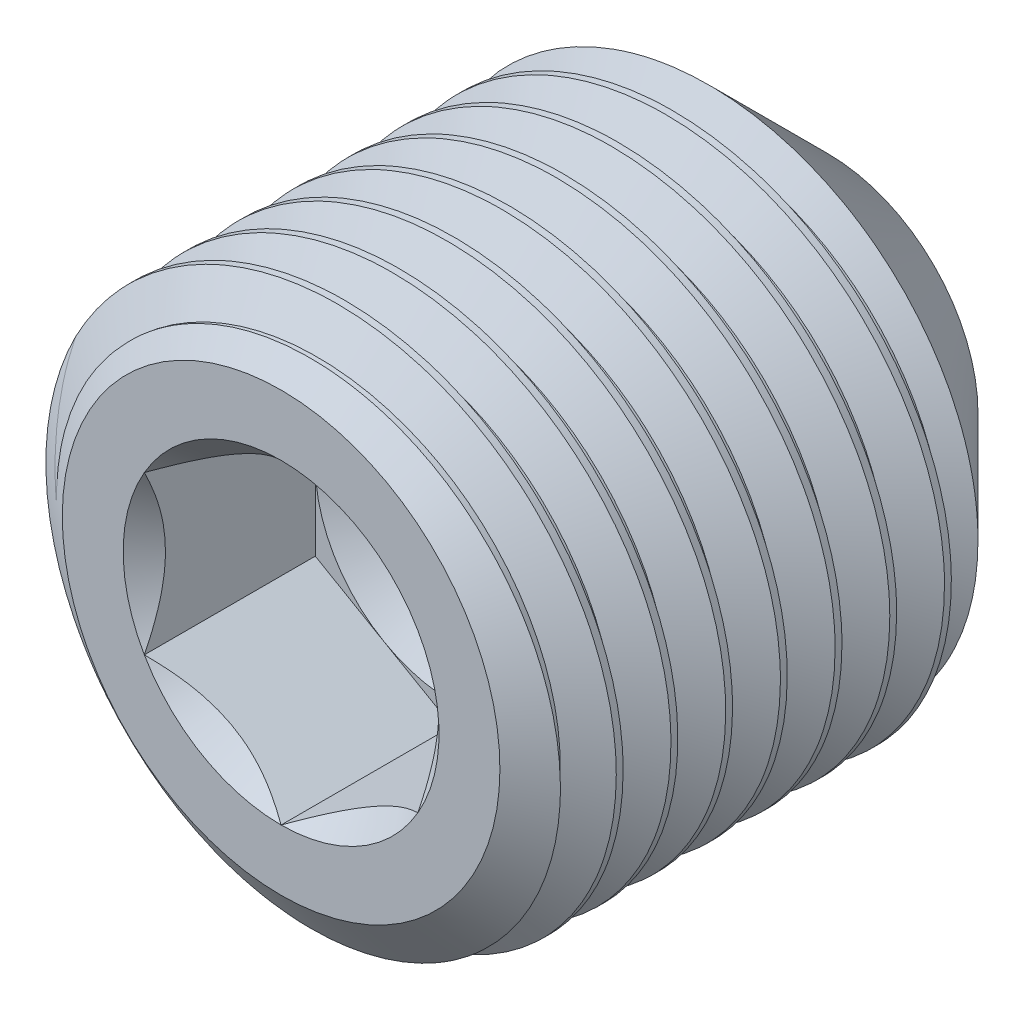
SolidWorks part; units mm, degrees
ref_plane "Front" through (0, 0, 0) normal (0, 0, 1) x (1, 0, 0)
ref_plane "Top" through (0, 0, 0) normal (0, 1, 0) x (1, 0, 0)
ref_plane "Right" through (0, 0, 0) normal (1, 0, 0) x (0, 0, -1)
sketch "Sketch22" plane through (0, 0, 0) normal (1, 0, 0) x (0, 0, -1)
  line L0 (-5.3046, 0) -> (-5.3046, 5.08)
  line L1 (-5.3046, 5.08) -> (-4.4154, 6.35)
  line L2 (-4.4154, 6.35) -> (4.5249, 6.35)
  line L3 (4.5249, 6.35) -> (7.3954, 3.4796)
  line L4 (7.3954, 3.4796) -> (5.3046, 0)
  line L5 (5.3046, 0) -> (-5.3046, 0)
  line L6 (5.3046, 0) -> (7.3954, 0) construction
  line L7 (7.3954, 0) -> (7.3954, 3.4796) construction
  line L8 (7.3954, -3.4796) -> (5.3046, 0) construction
  line L9 (-4.4154, -6.35) -> (4.5249, -6.35) construction
  dimension "Dia" = 12.7
  dimension "Length" = 12.7
  dimension "D3" = 35
  dimension "D5" = 118
  dimension "D6" = 45
  dimension "D7" = 10.16
revolve "Revolve1" add sketch "Sketch22" angle 360 about L6
ref_plane "Plane1" through (0, 0, -7.3954) normal (0, 0, 1) x (1, 0, 0)
sketch "Sketch27" plane through (0, 0, -7.3954) normal (0, 0, 1) x (1, 0, 0)
  circle A0 centre (0, 0) radius 6.35 construction
  circle A1 centre (0, 0) radius 6.35
curve "Helix/Spiral1" pitch 1.27 height 13.97 radius 6.35 centre (0, 0, -7.3954) axis (0, 0, 1) start towards (0, 1, 0)
sketch "Sketch28" plane through (0, 0, 0) normal (1, 0, 0) x (0, 0, -1)
  line L0 (7.3954, 6.35) -> (8.5066, 6.35)
  line L1 (8.5066, 6.35) -> (8.0304, 5.5251)
  line L2 (8.0304, 5.5251) -> (7.8716, 5.5251)
  line L3 (7.8716, 5.5251) -> (7.3954, 6.35)
  line L4 (7.6335, 5.9376) -> (8.2685, 5.9376) construction
  line L6 (-4.4154, 6.35) -> (4.5249, 6.35) construction
  line L7 (7.3954, 6.985) -> (7.3954, -6.985) construction
  dimension "D1" = 0.1588
  dimension "D2" = 0.635
  dimension "D3" = 60
sweep "Cut-Sweep2" cut profiles "Sketch28" path "Helix/Spiral1"
sketch "Sketch23" plane through (0, 0, 5.3046) normal (0, 0, 1) x (1, 0, 0)
  line L1 (0, 3.6662) -> (-3.175, 1.8331)
  line L2 (-3.175, 1.8331) -> (-3.175, -1.8331)
  line L3 (-3.175, -1.8331) -> (0, -3.6662)
  line L4 (0, -3.6662) -> (3.175, -1.8331)
  line L5 (3.175, -1.8331) -> (3.175, 1.8331)
  line L6 (3.175, 1.8331) -> (0, 3.6662)
  circle A0 centre (0, 0) radius 3.175 construction
  dimension "Hex" = 6.35
extrude "Cut-Extrude10" cut sketch "Sketch23" against normal blind 3.9688
sketch "Sketch24" plane through (0, 0, 5.3046) normal (0, 0, 1) x (1, 0, 0)
  circle A0 centre (0, 0) radius 3.6662
extrude "Cut-Extrude11" cut sketch "Sketch24" against normal through all draft 45
sketch "Sketch26" plane through (0, 0, 1.3359) normal (0, 0, 1) x (1, 0, 0)
  circle A0 centre (0, 0) radius 3.175 construction
  circle A1 centre (0, 0) radius 3.175
extrude "Cut-Extrude12" cut sketch "Sketch26" against normal through all draft 60
sketch "Sketch30" plane through (0, 0, 0) normal (1, 0, 0) x (0, 0, -1)
  line L0 (-4.4154, 6.35) -> (4.5249, 6.35) construction
  line L1 (-5.3046, 0) -> (-5.3046, 5.08) construction
  line L2 (7.3954, 0) -> (7.3954, 3.4796) construction
  line L3 (-4.4154, -6.35) -> (4.5249, -6.35) construction
  point P0 (-5.3046, 6.35)
  point P1 (7.3954, 6.35)
  point P2 (7.3954, -6.35)
  point P11 (2.9504, -6.35)
  dimension "D1" = 4.445
sketch "Sketch31" plane through (0, 0, 0) normal (1, 0, 0) x (0, 0, -1)
  line L2 (5.3046, 0) -> (7.3954, -3.4796)
  line L3 (7.3954, 3.4796) -> (5.3046, 0)
equation "\"D7@Sketch22\"=\"Dia@Sketch22\"*.8"
equation "\"D1@Sketch28\" = \"D4@Helix/Spiral1\" * .125"
equation "\"D3@Helix/Spiral1\" = \"Length@Sketch22\" + \"D4@Helix/Spiral1\""
equation "\"D1@Sketch30\" = \"D4@Helix/Spiral1\" * 3.5"
equation "\"hex Depth@Cut-Extrude10\" = \"Hex@Sketch23\" * .625"
equation "\"D2@Sketch28\" = \"D4@Helix/Spiral1\" * .5"
